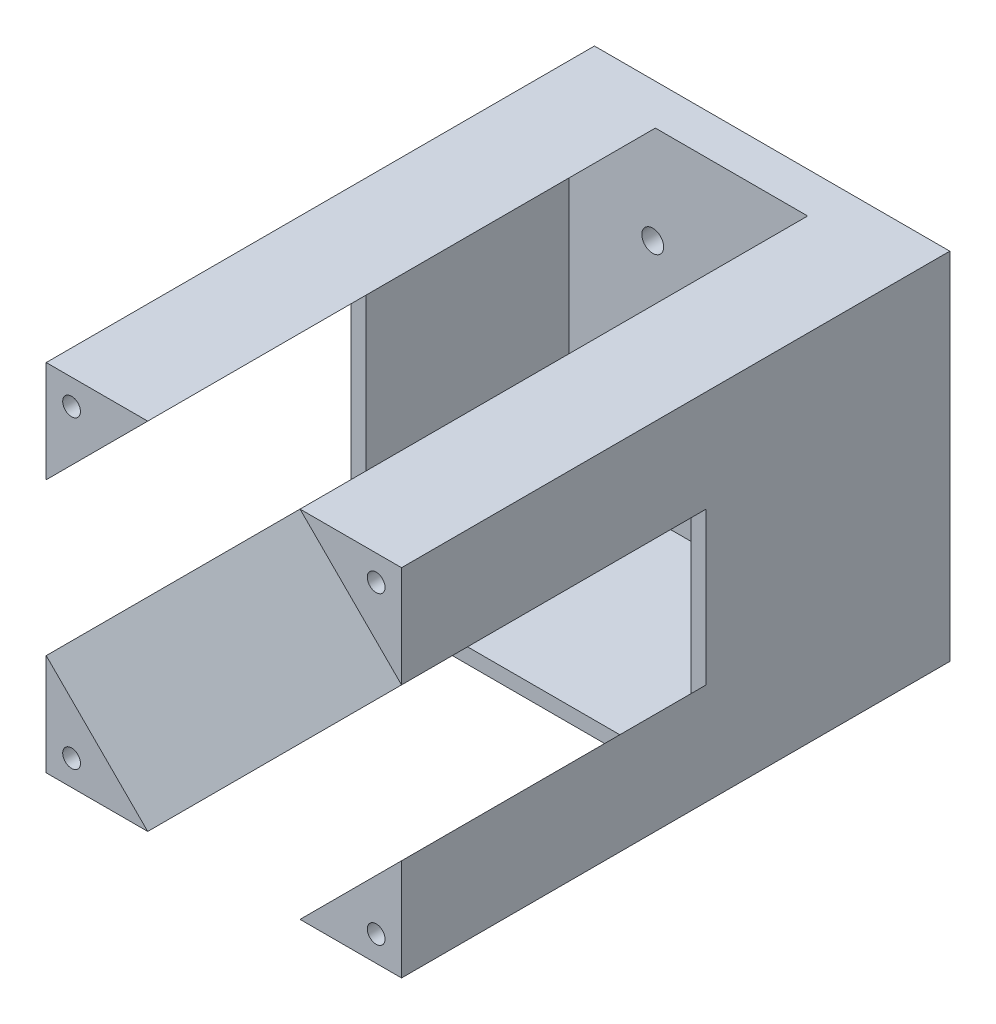
SolidWorks part; units mm, degrees
ref_plane "Piano frontale" through (0, 0, 0) normal (1, 0, 0) x (0, 1, 0)
ref_plane "Piano superiore" through (0, 0, 0) normal (0, 0, 1) x (0, 1, 0)
ref_plane "Piano destro" through (0, 0, 0) normal (0, 1, 0) x (-1, 0, 0)
sketch "Schizzo1" plane through (0, 0, 0) normal (0, 0, 1) x (0, 1, 0)
  line L1 (-35, -35) -> (35, -35)
  line L2 (-35, -35) -> (-35, 35)
  line L3 (-35, 35) -> (35, 35)
  line L4 (35, -35) -> (35, 35)
  line L5 (-35, -35) -> (35, 35) construction
  line L6 (-35, 35) -> (35, -35) construction
  point P0 (0, 0)
  dimension "D1" = 70
extrude "Estrusione-Estrusione2" add sketch "Schizzo1" along normal blind 8 contours L2 L3 L4 L1
hole_wizard "Foro per Vite M6-1" positions "Schizzo11" profile "Schizzo12" hole size "M6" standard "ISO"
sketch "Schizzo11" plane through (0, 0, 8) normal (0, 0, 1) x (1, 0, 0)
  point P0 (0, 0)
sketch "Schizzo12" plane through (0, 0, 8) normal (1, 0, 0) x (0, -1, 0)
  line L0 (0, 0) -> (0, 11.9828)
  line L1 (0, 11.9828) -> (3.3, 10)
  line L2 (3.3, 10) -> (3.3, 0)
  line L5 (3.3, 0) -> (0, 0)
  line L10 (0, 11.9828) -> (-3.3, 10) construction
  line L11 (0, -6.35) -> (0, 107.95) construction
  dimension "Hole Dia." = 6.6
  dimension "Hole Depth" = 10
  dimension "Drill Angle" = 118
hole_wizard "Foro per Vite M4-1" positions "Schizzo13" profile "Schizzo14" hole size "M4" standard "ISO" end condition through all
sketch "Schizzo13" plane through (0, 0, 8) normal (0, 0, 1) x (1, 0, 0)
  line L1 (-15.52, -15.52) -> (15.52, -15.52)
  line L2 (-15.52, -15.52) -> (-15.52, 15.52)
  line L3 (-15.52, 15.52) -> (15.52, 15.52)
  line L4 (15.52, -15.52) -> (15.52, 15.52)
  line L5 (-15.52, -15.52) -> (15.52, 15.52) construction
  line L6 (-15.52, 15.52) -> (15.52, -15.52) construction
  point P1 (0, 0)
  point P2 (15.52, 15.52)
  point P5 (-15.52, -15.52)
  point P6 (-15.52, 15.52)
  point P7 (15.52, -15.52)
  point P35 (-15.52, 15.52)
  dimension "D1" = 31.04
sketch "Schizzo14" plane through (0, 0, 8) normal (1, 0, 0) x (0, -1, 0)
  line L0 (0, 0) -> (0, 8)
  line L1 (0, 8) -> (2.15, 8)
  line L2 (2.15, 8) -> (2.15, 0)
  line L5 (2.15, 0) -> (0, 0)
  line L11 (0, -6.35) -> (0, 107.95) construction
  dimension "Thru Hole Dia." = 4.3
  dimension "Thru Hole Depth" = 8
sketch "Schizzo20" plane through (0, 0, 8) normal (0, 0, 1) x (1, 0, 0)
  line L0 (-35, 35) -> (-35, 15)
  line L1 (-35, 15) -> (-15, 35)
  line L2 (-15, 35) -> (-35, 35)
  dimension "D1" = 20
extrude "Estrusione-Estrusione5" add sketch "Schizzo20" along normal blind 100
hole_wizard "Foro Ø0.15 (3.5)-1" positions "Schizzo21" profile "Schizzo22" hole size "Ø0.15" standard "ISO"
sketch "Schizzo21" plane through (0, 0, 108) normal (0, 0, 1) x (1, 0, 0)
  line L1 (-35, 35) -> (-30, 35)
  line L2 (-35, 35) -> (-35, 30)
  line L3 (-35, 30) -> (-30, 30)
  line L4 (-30, 35) -> (-30, 30)
  point P1 (-30, 30)
  dimension "D1" = 5
sketch "Schizzo22" plane through (-30, 30, 108) normal (1, 0, 0) x (0, -1, 0)
  line L0 (0, 0) -> (0, 15)
  line L1 (0, 15) -> (1.75, 15)
  line L2 (1.75, 15) -> (1.75, 0)
  line L5 (1.75, 0) -> (0, 0)
  line L10 (0, 15) -> (-1.75, 15) construction
  line L11 (0, -6.35) -> (0, 107.95) construction
  dimension "Hole Dia." = 3.5
  dimension "Hole Depth" = 15
  dimension "Drill Angle" = 180
ref_plane "Piano2" through (0, 0, 105) normal (0, 0, 1) x (1, 0, 0)
sketch "Schizzo24" plane through (0, 0, 105) normal (0, 0, 1) x (1, 0, 0)
  line L6 (-15, 35) -> (-35, 35) construction
  line L7 (-26.8246, 30) -> (-28.4123, 32.75)
  line L8 (-28.4123, 32.75) -> (-31.5877, 32.75)
  line L9 (-31.5877, 32.75) -> (-33.1754, 30)
  line L10 (-33.1754, 30) -> (-31.5877, 27.25)
  line L11 (-31.5877, 27.25) -> (-28.4123, 27.25)
  line L12 (-28.4123, 27.25) -> (-26.8246, 30)
  circle A0 centre (-30, 30) radius 2.75 construction
  circle A1 centre (-30, 30) radius 1.75 construction
  dimension "D1" = 5.5
ref_plane "Piano1" through (-31, 0, 0) normal (-1, 0, 0) x (0, 0, 1)
ref_axis "Assi1" through (-31, 19, -5.4) along (0, 0, 1)
extrude "Taglio-Estrusione2" cut sketch "Schizzo24" against normal blind 2.6
pattern_circular "RipetizioneCircolare28" count 4 over 360 about axis through (0, 0, 8) along (0, 0, 1) of "Estrusione-Estrusione5", "Foro Ø0.15 (3.5)-1", "Taglio-Estrusione2"
sketch "Schizzo29" plane through (-35, 0, 0) normal (-1, 0, 0) x (0, -1, 0)
  line L0 (15, 8) -> (-15, 8) construction
  line L1 (-19, 48) -> (19, 48)
  line L2 (-19, 48) -> (-19, 8)
  line L3 (-19, 8) -> (19, 8)
  line L4 (19, 48) -> (19, 8)
  line L5 (-19, -5.4) -> (-19, 113.4) construction
  point P4 (0, 8)
  point P7 (0, 8)
  dimension "D1" = 40
extrude "Estrusione-Estrusione9" add sketch "Schizzo29" against normal blind 3
pattern_circular "RipetizioneCircolare30" count 3 over 180 about axis through (0, 0, 8) along (0, 0, 1) of "Estrusione-Estrusione9"
